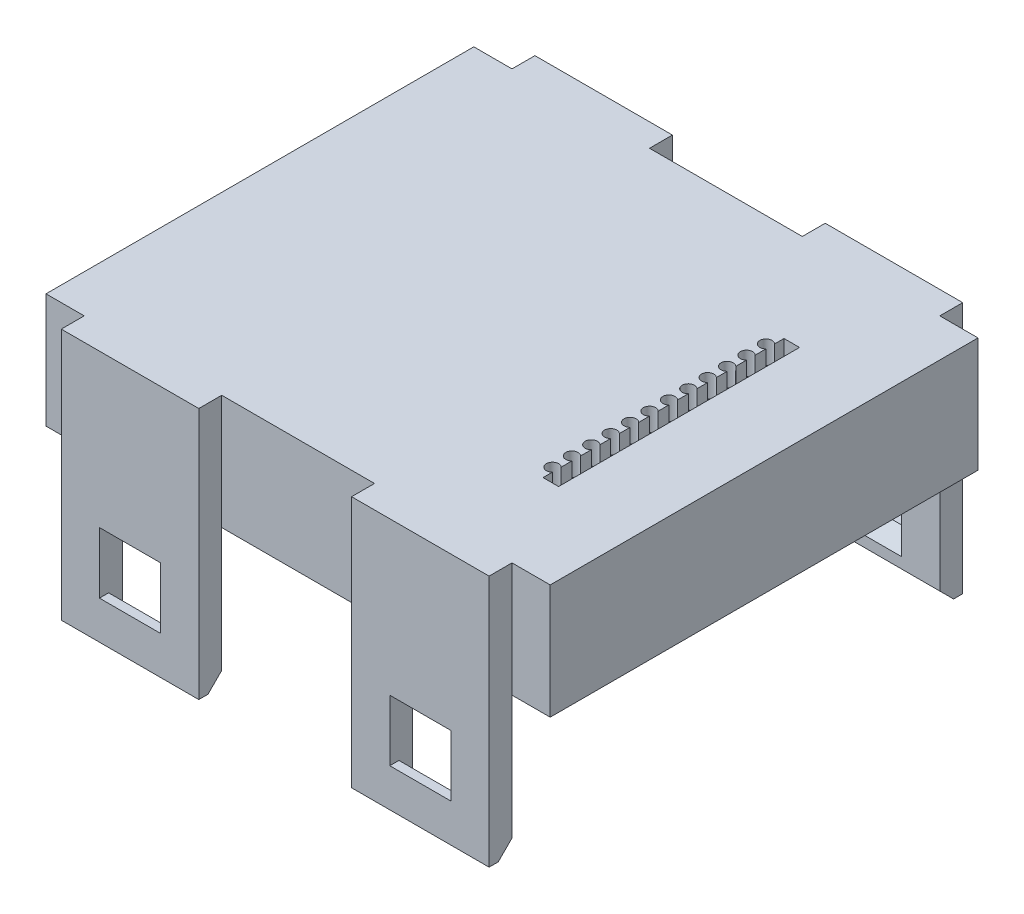
SolidWorks part; units mm, degrees
ref_plane "Front Plane" through (0, 0, 0) normal (0, 0, 1) x (1, 0, 0)
ref_plane "Top Plane" through (0, 0, 0) normal (0, 1, 0) x (1, 0, 0)
ref_plane "Right Plane" through (0, 0, 0) normal (1, 0, 0) x (0, 0, -1)
sketch "Sketch1" plane through (0, 0, 0) normal (0, 1, 0) x (1, 0, 0)
  line L1 (-33, -28) -> (33, -28)
  line L2 (-33, -28) -> (-33, 28)
  line L3 (-33, 28) -> (33, 28)
  line L4 (33, -28) -> (33, 28)
  line L5 (-33, -28) -> (33, 28) construction
  line L6 (-33, 28) -> (33, -28) construction
  point P0 (0, 0)
  dimension "D1" = 66
  dimension "D2" = 56
extrude "Base" add sketch "Sketch1" against normal blind 3
sketch "Sketch4" plane through (0, 0, 0) normal (0, 1, 0) x (1, 0, 0)
  line L1 (-33, 28) -> (33, 28)
  line L2 (-33, 28) -> (-33, -28)
  line L3 (-33, -28) -> (33, -28)
  line L4 (33, 28) -> (33, -28)
  line L5 (-33, 28) -> (33, -28) construction
  line L6 (-33, -28) -> (33, 28) construction
  line L7 (-29, 24) -> (29, 24)
  line L8 (-29, 24) -> (-29, -24)
  line L9 (-29, -24) -> (29, -24)
  line L10 (29, 24) -> (29, -24)
  line L11 (-29, 24) -> (29, -24) construction
  line L12 (-29, -24) -> (29, 24) construction
  point P0 (0, 0)
  point P7 (0, 0)
  dimension "D1" = 48
  dimension "D2" = 58
extrude "Wall1" add sketch "Sketch4" against normal blind 12 from surface starting at face at (0, -3, 0)
sketch "Sketch8" plane through (0, 0, 0) normal (0, 1, 0) x (1, 0, 0)
  line L1 (-31, 26) -> (31, 26)
  line L2 (-31, 26) -> (-31, -26)
  line L3 (-31, -26) -> (31, -26)
  line L4 (31, 26) -> (31, -26)
  line L5 (-31, 26) -> (31, -26) construction
  line L6 (-31, -26) -> (31, 26) construction
  line L7 (-29, 24) -> (29, 24)
  line L8 (-29, 24) -> (-29, -24)
  line L9 (-29, -24) -> (29, -24)
  line L10 (29, 24) -> (29, -24)
  line L11 (-29, 24) -> (29, -24) construction
  line L12 (-29, -24) -> (29, 24) construction
  point P0 (0, 0)
  point P6 (0, 0)
  dimension "D1" = 52
  dimension "D2" = 62
extrude "Wall2" add sketch "Sketch8" against normal blind 2 from surface starting at face at (0, -15, 0)
sketch "Sketch9" plane through (0, 0, 0) normal (0, 1, 0) x (1, 0, 0)
  line L1 (-23, 8.5) -> (13, 8.5)
  line L2 (-23, 8.5) -> (-23, -8.5)
  line L3 (-23, -8.5) -> (13, -8.5)
  line L5 (13, -8.5) -> (13, -10.5)
  line L6 (13, 8.5) -> (13, 10.5)
  line L7 (-25, 10.5) -> (13, 10.5)
  line L8 (-25, 10.5) -> (-25, -10.5)
  line L9 (-25, -10.5) -> (13, -10.5)
  line L10 (-29, 0) -> (-25, 0) construction
  line L11 (-29, -24) -> (-29, 24) construction
  point P0 (0, 0)
  point P6 (0, 0)
  dimension "D1" = 36
  dimension "D2" = 17
  dimension "D3" = 38
  dimension "D4" = 21
  dimension "D5" = 38
  dimension "D6" = 4
extrude "BatteryWall" add sketch "Sketch9" against normal blind 8 from surface starting at face at (0, -3, 0)
sketch "Sketch10" plane through (0, 0, 0) normal (0, 1, 0) x (1, 0, 0)
  line L0 (29, -24) -> (-29, -24) construction
  line L1 (-10, 24) -> (10, 24)
  line L2 (-10, 24) -> (-10, -24)
  line L3 (-10, -24) -> (10, -24)
  line L4 (10, 24) -> (10, -24)
  line L5 (-10, 24) -> (10, -24) construction
  line L6 (-10, -24) -> (10, 24) construction
  point P0 (0, 0)
  dimension "D1" = 20
extrude "BatteryHolder" add sketch "Sketch10" against normal blind 2 from surface starting at face at (-5.5, -11, 0)
sketch "Sketch15" plane through (0, 0, 0) normal (0, 1, 0) x (1, 0, 0)
  line L1 (13, -2.4893) -> (14, -2.4893)
  line L2 (13, -2.4893) -> (13, 2.5107)
  line L3 (13, 2.5107) -> (14, 2.5107)
  line L4 (14, -2.4893) -> (14, 2.5107)
  point P5 (13, 0.0107)
  dimension "D1" = 5
  dimension "D2" = 1
extrude "BatteryNotch" add sketch "Sketch15" against normal blind 1.2 from surface starting at face at (0, -3, 0)
fillet "BatteryNotch2" radius 1 4 edges at (13.5, -4.2, -2.5107) (13, -4.2, -0.0107) (13.5, -4.2, 2.4893) (14, -4.2, -0.0107)
sketch "Sketch11" plane through (0, 0, 0) normal (0, 0, 1) x (1, 0, 0)
  line L0 (0, 0) -> (0, -16.5) construction
  line L1 (0, -16.5) -> (-19, -16.5) construction
  line L2 (0, -16.5) -> (19, -16.5) construction
  line L3 (34.1, 0) -> (-34.1, 0) construction
  line L4 (-28, -33) -> (-10, -33)
  line L5 (-28, -33) -> (-28, 0)
  line L6 (-28, 0) -> (-10, 0)
  line L7 (-10, -33) -> (-10, 0)
  line L8 (-28, -33) -> (-10, 0) construction
  line L9 (-28, 0) -> (-10, -33) construction
  line L10 (-19, -33) -> (-19, -28) construction
  line L11 (10, -33) -> (28, -33)
  line L12 (10, -33) -> (10, 0)
  line L13 (10, 0) -> (28, 0)
  line L14 (28, -33) -> (28, 0)
  line L15 (10, -33) -> (28, 0) construction
  line L16 (10, 0) -> (28, -33) construction
  line L17 (-28, -25.0429) -> (-23, -25.0429) construction
  line L18 (-23, -20) -> (-23, -28)
  line L19 (-23, -20) -> (-15, -20)
  line L20 (-23, -28) -> (-15, -28)
  line L21 (-15, -20) -> (-15, -28)
  line L22 (10, -25.0429) -> (15, -25.0429) construction
  line L23 (19, -33) -> (19, -28) construction
  line L24 (15, -20) -> (15, -28)
  line L25 (15, -20) -> (23, -20)
  line L26 (15, -28) -> (23, -28)
  line L27 (23, -20) -> (23, -28)
  dimension "D1" = 19
  dimension "D2" = 19
  dimension "D3" = 18
  dimension "D4" = 33
  dimension "D5" = 18
  dimension "D6" = 5
  dimension "D7" = 5
  dimension "D8" = 8
  dimension "D9" = 8
  dimension "D10" = 5
  dimension "D11" = 5
  dimension "D12" = 8
  dimension "D13" = 8
extrude "Clips1" add sketch "Sketch11" along normal blind 3 from surface starting at face at (0, -7.5, 28)
extrude "Clips2" add sketch "Sketch11<2>" against normal blind 3 from surface starting at face at (0, -7.5, -28)
sketch "Sketch11<2>" plane through (0, 0, 0) normal (0, 0, 1) x (1, 0, 0) same geometry as "Sketch11"
chamfer "Chamfer3" distance 1.8 angle 45 8 edges at (-19, -28, -28) (19, -28, -28) (19, -28, 28) (-19, -28, 28) (19, -33, -28) (-19, -33, -28) (19, -33, 28) (-19, -33, 28)
sketch "Sketch12" plane through (0, 0, 0) normal (0, 1, 0) x (1, 0, 0)
  line L0 (29, -14.5) -> (19.8, -14.5) construction
  line L1 (29, 24) -> (29, -24) construction
  line L2 (19.8, -14.5) -> (19.8, -24) construction
  line L3 (29, -24) -> (-29, -24) construction
  line L4 (19.8, -14.5) -> (19.8, 13.44) construction
  line L5 (20.6, 13.44) -> (22.6, 13.44) construction
  line L10 (17, 16.24) -> (22.6, -17.3) construction
  line L11 (17, -17.3) -> (22.6, 16.24) construction
  line L12 (19.8, 14.24) -> (19.8, 16.24) construction
  line L13 (19.8, 13.44) -> (20.3657, 14.0057) construction
  line L14 (20.3657, 14.0057) -> (20.3657, 12.8743) construction
  line L15 (20.3657, 12.8743) -> (19.8, 13.44) construction
  circle A0 centre (19.8, -14.5) radius 0.8
  circle A1 centre (19.8, -11.96) radius 0.8
  circle A2 centre (19.8, -9.42) radius 0.8
  circle A3 centre (19.8, -6.88) radius 0.8
  circle A4 centre (19.8, -4.34) radius 0.8
  circle A5 centre (19.8, -1.8) radius 0.8
  circle A6 centre (19.8, 0.74) radius 0.8
  circle A7 centre (19.8, 3.28) radius 0.8
  circle A8 centre (19.8, 5.82) radius 0.8
  circle A9 centre (19.8, 8.36) radius 0.8
  circle A10 centre (19.8, 10.9) radius 0.8
  circle A11 centre (19.8, 13.44) radius 0.8
  point P10 (19.8, -0.53)
  dimension "D3" = 1.6
  dimension "D5" = 2
  dimension "D1" = 9.5
  dimension "D2" = 9.2
  dimension "D4" = 12
  dimension "D6" = 2
extrude "WireSlots" cut sketch "Sketch12" along normal through all from surface starting at face at (0, -3, 0)
sketch "Sketch13" plane through (0, 0, 0) normal (0, 1, 0) x (1, 0, 0)
  line L0 (19.8, 14.24) -> (19.8, 15.24) construction
  line L1 (20.3657, 15.24) -> (19.8, -1.53) construction
  line L3 (22.4, 15.24) -> (22.4, -16.3)
  line L6 (19.8, -1.53) -> (20.3657, -16.3) construction
  line L7 (22.4, -16.3) -> (19.8, -1.53) construction
  line L8 (20.6, -14.5) -> (22.4, -14.5) construction
  line L9 (19.8, 13.44) -> (20.3657, 12.8743) construction
  line L10 (19.8, 13.44) -> (20.3657, 14.0057) construction
  line L11 (20.3657, 14.0057) -> (20.3657, 12.8743) construction
  line L12 (20.3657, 15.24) -> (20.3657, -16.3)
  line L13 (20.3657, -16.3) -> (22.4, -16.3)
  line L14 (20.3657, 15.24) -> (22.4, 15.24)
  line L15 (19.8, -1.53) -> (22.4, 15.24) construction
  line L16 (19.8, 15.24) -> (20.3657, 15.24) construction
  line L17 (19.8, -15.3) -> (19.8, -16.3) construction
  line L18 (19.8, -16.3) -> (20.3657, -16.3) construction
  circle A0 centre (19.8, 13.44) radius 0.8 construction
  circle A1 centre (19.8, -14.5) radius 0.8 construction
  point P7 (19.8, -0.53)
  dimension "D1" = 1
  dimension "D2" = 1.8
  dimension "D3" = 1
extrude "WireSlots2" cut sketch "Sketch13" along normal through all from surface starting at face at (19.8, -3, 13.7)
